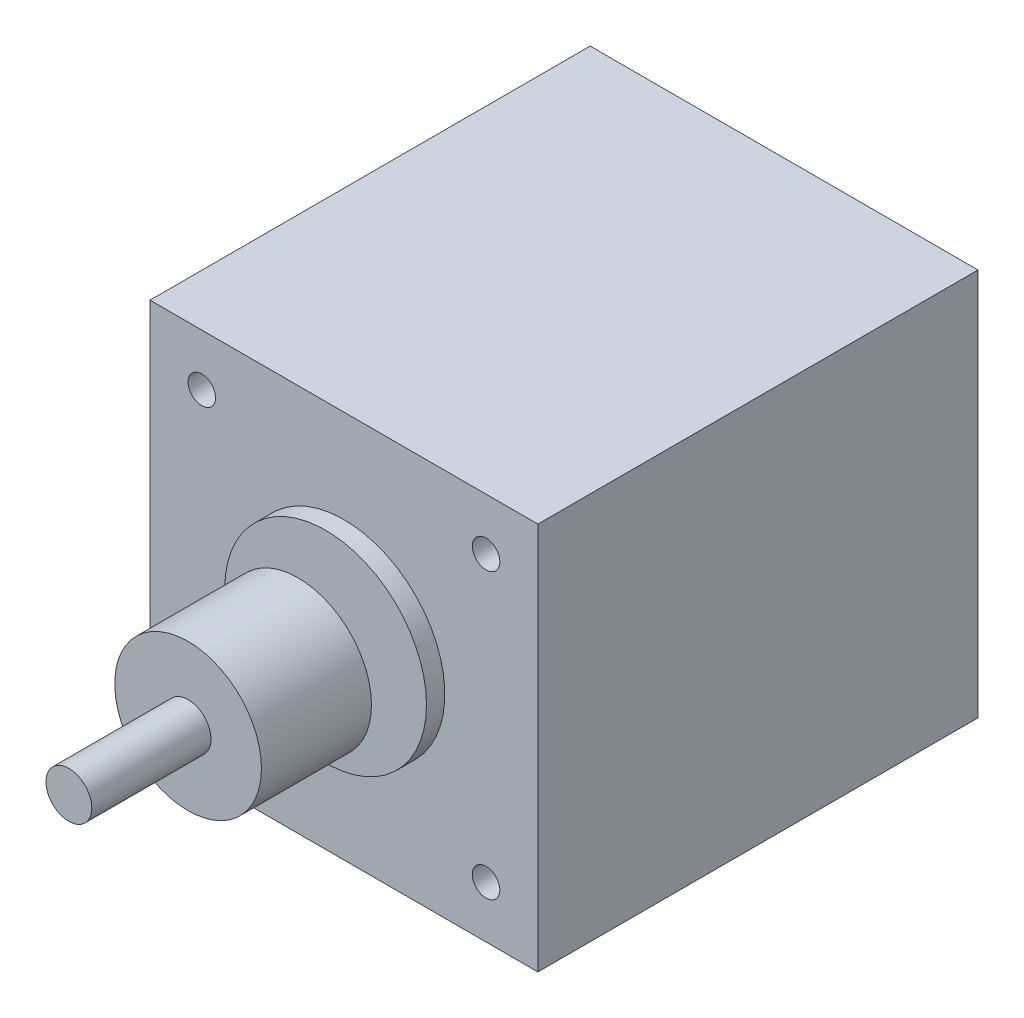
SolidWorks part; units mm, degrees
ref_plane "Спереди" through (0, 0, 0) normal (0, 0, 1) x (1, 0, 0)
ref_plane "Сверху" through (0, 0, 0) normal (0, 1, 0) x (1, 0, 0)
ref_plane "Справа" through (0, 0, 0) normal (1, 0, 0) x (0, 0, -1)
other "Configuration Table"
sketch "Эскиз1" plane through (0, 0, 0) normal (0, 0, 1) x (1, 0, 0)
  line L1 (-21.15, -21.15) -> (21.15, -21.15)
  line L2 (-21.15, -21.15) -> (-21.15, 21.15)
  line L3 (-21.15, 21.15) -> (21.15, 21.15)
  line L4 (21.15, -21.15) -> (21.15, 21.15)
  line L5 (-21.15, -21.15) -> (21.15, 21.15) construction
  line L6 (-21.15, 21.15) -> (21.15, -21.15) construction
  point P0 (0, 0)
  dimension "D1" = 42.3
  dimension "D2" = 42.3
extrude "Корпус" add sketch "Эскиз1" along normal blind 48
sketch "Эскиз2" plane through (0, 0, 0) normal (0, 0, 1) x (1, 0, 0)
  circle A0 centre (0, 0) radius 2.5
extrude "Вал_ПРЕДВ" add sketch "Эскиз2" along normal blind 78
sketch "Эскиз3" plane through (0, 0, 0) normal (0, 0, 1) x (1, 0, 0)
  circle A0 centre (0, 0) radius 11
  dimension "D1" = 22
extrude "Буртик_ПРЕДВ" add sketch "Эскиз3" along normal blind 50
sketch "Эскиз4" plane through (0, 0, 0) normal (0, 0, 1) x (1, 0, 0)
  circle A0 centre (0, 0) radius 8
  dimension "D1" = 16
extrude "Шкив_габарит_ПРЕДВ" add sketch "Эскиз4" along normal blind 12 from offset 53
sketch "Эскиз5" plane through (0, 0, 0) normal (0, 0, 1) x (1, 0, 0)
  circle A0 centre (-15.5, -15.5) radius 1.5
  circle A1 centre (-15.5, 15.5) radius 1.5
  circle A2 centre (15.5, -15.5) radius 1.5
  circle A3 centre (15.5, 15.5) radius 1.5
  dimension "D2" = 3
  dimension "D3" = 3
  dimension "D4" = 3
extrude "Крепеж_М3_ПРЕДВ" cut sketch "Эскиз5" against normal blind 4.5 from offset 48
equation "\"Мотор X ширина корпуса\"= 42.3"
equation "\"Мотор X высота корпуса\"= 42.3"
equation "\"Мотор X длина корпуса\"= 40"
equation "\"Мотор X вылет вала\"= 19.8"
equation "\"Мотор Y ширина корпуса\"= 42.3"
equation "\"Мотор Y высота корпуса\"= 42.3"
equation "\"Мотор Y длина корпуса\"= 48"
equation "\"Мотор Y вылет вала\"= 30"
equation "\"Мотор Z ширина корпуса\"= 42"
equation "\"Мотор Z высота корпуса\"= 42"
equation "\"Мотор Z длина корпуса\"= 40"
equation "\"Мотор Z вылет вала\"= 23"
equation "\"Мотор диаметр вала ПРЕДВ\"= 5"
equation "\"Мотор шаг крепления ПРЕДВ\"= 31"
equation "\"Мотор диаметр отверстий ПРЕДВ\"= 3"
equation "\"Мотор глубина отверстий ПРЕДВ\"= 4.5"
equation "\"Мотор диаметр буртика ПРЕДВ\"= 22"
equation "\"Мотор высота буртика ПРЕДВ\"= 2"
equation "\"Мотор диаметр шкива ПРЕДВ\"= 16"
equation "\"Мотор длина шкива ПРЕДВ\"= 12"
equation "\"Мотор отступ шкива ПРЕДВ\"= 5"
equation "\"Мотор X шаг градусов\"= 1.8"
equation "\"Мотор X ток А\"= 1.5"
equation "\"Мотор X сопротивление Ом\"= 1.3"
equation "\"Мотор X индуктивность мГн\"= 2"
equation "\"Мотор Y шаг градусов\"= 1.8"
equation "\"Мотор Y ток А\"= 2.2"
equation "\"Мотор Y сопротивление Ом\"= 0.9"
equation "\"Мотор Y индуктивность мГн\"= 2"
equation "\"Мотор Z шаг градусов\"= 1.8"
equation "\"Мотор Z ток А\"= 1"
equation "\"Мотор Z сопротивление Ом\"= 4"
equation "\"Мотор Z индуктивность мГн\"= 8"
equation "\"Мотор Y диаметр ротора\"= 25.78"
equation "\"D1@Эскиз1\" = \"Мотор Y ширина корпуса\""
equation "\"D2@Эскиз1\" = \"Мотор Y высота корпуса\""
equation "\"D1@Корпус\" = \"Мотор Y длина корпуса\""
equation "\"D1@Эскиз2\" = \"Мотор диаметр вала ПРЕДВ\""
equation "\"D1@Вал_ПРЕДВ\" = \"Мотор Y длина корпуса\" + \"Мотор Y вылет вала\""
equation "\"D1@Эскиз3\" = \"Мотор диаметр буртика ПРЕДВ\""
equation "\"D1@Буртик_ПРЕДВ\" = \"Мотор Y длина корпуса\" + \"Мотор высота буртика ПРЕДВ\""
equation "\"D1@Эскиз4\" = \"Мотор диаметр шкива ПРЕДВ\""
equation "\"D1@Шкив_габарит_ПРЕДВ\" = \"Мотор длина шкива ПРЕДВ\""
equation "\"D19@Шкив_габарит_ПРЕДВ\" = \"Мотор Y длина корпуса\" + \"Мотор отступ шкива ПРЕДВ\""
equation "\"D1@Эскиз5\" = \"Мотор диаметр отверстий ПРЕДВ\""
equation "\"D2@Эскиз5\" = \"Мотор диаметр отверстий ПРЕДВ\""
equation "\"D3@Эскиз5\" = \"Мотор диаметр отверстий ПРЕДВ\""
equation "\"D4@Эскиз5\" = \"Мотор диаметр отверстий ПРЕДВ\""
equation "\"D1@Крепеж_М3_ПРЕДВ\" = \"Мотор глубина отверстий ПРЕДВ\""
equation "\"D19@Крепеж_М3_ПРЕДВ\" = \"Мотор Y длина корпуса\""
equation "\"Ширина груза\"= 420"
equation "\"Глубина груза\"= 490"
equation "\"Высота груза\"= 297"
equation "\"Ширина ячейки\"= \"Ширина груза\" + 10"
equation "\"Глубина ячейки\"= \"Глубина груза\" + 10"
equation "\"Высота ячейки\"= \"Высота груза\" + 10 + 13"
equation "\"Колво ячеек ширина\"= 2"
equation "\"Колво ячеек высота\"= 2"
equation "\"Толщина стенки\"= 10"
equation "\"Крепление дверцы\"= 5"
equation "\"Ширина рейки\"= \"Толщина шестерни\""
equation "\"Высота рейки\"= 20"
equation "\"Высота пола\"= 20"
equation "\"Колво полозьев\"= 5"
equation "\"Отступ рейки\"= 20"
equation "\"Глубина каретки\"= \"Глубина ячейки\" + 80"
equation "\"Отступ шпильки\"= 20"
equation "\"Диаметр шпильки\"= 5"
equation "\"Длинна шпильки\"= ( \"Высота ячейки\" + \"Толщина стенки\" + \"Высота пола\" ) * \"Колво ячеек высота\" + ( \"Толщина стенки\" + \"Отступ рейки\" ) * 2"
equation "\"Ширина пластины\"= 50  "
equation "\"Высота зона выгрузки\"= \"Высота ячейки\" * 2 + \"Толщина стенки\" * 2"
equation "\"Колво выгрузки\"= 1"
equation "\"Отступ крепления мотора фиксации\" = 30"
equation "\"Диаметр оси\"= 10"
equation "\"Диаметр ролика\"= 20"
equation "\"Колво роликов\"= 10"
equation "\"Шаг роликов\"= \"Диаметр ролика\" + 20"
equation "\"Ширина ячейки выгрузки\"= \"Ширина ячейки\" + \"Толщина стенки\" + \"Отступ крепления мотора фиксации\"*2"
equation "\"Длинна рейки\"= ( \"Ширина ячейки\" + \"Толщина стенки\" + \"Крепление дверцы\" ) * \"Колво ячеек ширина\" + \"Ширина ячейки выгрузки\" * \"Колво выгрузки\" + \"Толщина стенки\""
